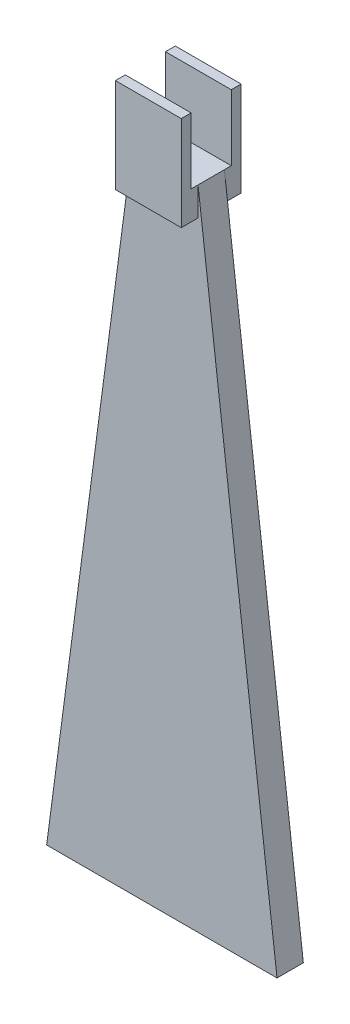
SolidWorks part; units mm, degrees
material "Gray Cast Iron"
ref_plane "Front Plane" through (0, 0, 0) normal (0, 0, 1) x (1, 0, 0)
ref_plane "Top Plane" through (0, 0, 0) normal (0, 1, 0) x (1, 0, 0)
ref_plane "Right Plane" through (0, 0, 0) normal (1, 0, 0) x (0, 0, -1)
sketch "Sketch1" plane through (0, 0, 0) normal (0, 0, 1) x (1, 0, 0)
  line L0 (-115, 0) -> (-45, 0)
  line L1 (-45, 0) -> (-69, 196.7)
  line L2 (-69, 196.7) -> (-89, 196.7)
  line L3 (-89, 196.7) -> (-115, 0)
extrude "Boss-Extrude1" add sketch "Sketch1" along normal mid plane 8
sketch "Sketch2" plane through (0, 0, 0) normal (0, 1, 0) x (1, 0, 0)
  line L0 (-89, -9.1) -> (-69, -9.1)
  line L1 (-69, -9.1) -> (-69, 9.1)
  line L2 (-69, 9.1) -> (-89, 9.1)
  line L3 (-89, 9.1) -> (-89, -9.1)
extrude "Boss-Extrude2" add sketch "Sketch2" along normal blind 8.7 from offset 188
sketch "Sketch3" plane through (0, 0, 0) normal (0, 1, 0) x (1, 0, 0)
  line L0 (-89, 6.1) -> (-69, 6.1)
  line L1 (-89, 9.1) -> (-89, 4) construction
  line L2 (-69, 4) -> (-69, 9.1) construction
  line L3 (-69, 6.1) -> (-69, 9.1)
  line L4 (-69, 9.1) -> (-89, 9.1)
  line L5 (-89, 9.1) -> (-89, 6.1)
  line L6 (-89, -6.1) -> (-69, -6.1)
  line L7 (-89, -4) -> (-89, -9.1) construction
  line L8 (-69, -9.1) -> (-69, -4) construction
  line L9 (-69, -6.1) -> (-69, -9.1)
  line L10 (-69, -9.1) -> (-89, -9.1)
  line L11 (-89, -9.1) -> (-89, -6.1)
extrude "Boss-Extrude3" add sketch "Sketch3" along normal blind 20 from offset 196.7
